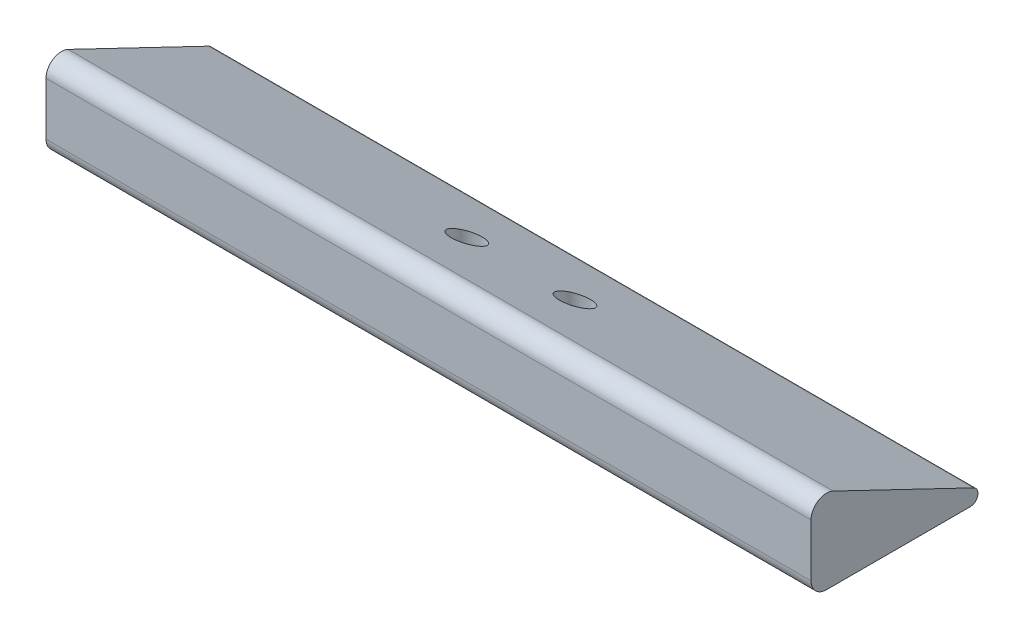
SolidWorks part; units mm, degrees
material "Rubber"
ref_plane "Front Plane" through (0, 0, 0) normal (0, 0, 1) x (1, 0, 0)
ref_plane "Top Plane" through (0, 0, 0) normal (0, 1, 0) x (1, 0, 0)
ref_plane "Right Plane" through (0, 0, 0) normal (1, 0, 0) x (0, 0, -1)
sketch "Sketch1" plane through (0, 0, 0) normal (1, 0, 0) x (0, 0, -1)
  line L0 (2, 0) -> (20.6058, 0)
  line L1 (21.0385, 1.9015) -> (2.8655, 10.6246)
  line L2 (0, 8.8215) -> (0, 2)
  arc A0 (0, 8.8215) -> (2.8655, 10.6246) centre (2, 8.8215) cw
  arc A1 (2, 0) -> (0, 2) centre (2, 2) cw
  arc A2 (21.0385, 1.9015) -> (20.6058, 0) centre (20.6058, 1) cw
  point P6 (0, 12)
  point P9 (0, 0)
  point P12 (25, 0)
  dimension "D1" = 12
  dimension "D3" = 2
  dimension "D4" = 1
  dimension "D2" = 25
extrude "Boss-Extrude1" add sketch "Sketch1" along normal blind 99
ref_plane "Plane1" through (0, 10, 0) normal (0, 1, 0) x (1, 0, 0)
sketch "Sketch2" plane through (0, 10, 0) normal (0, 1, 0) x (1, 0, 0)
  line L0 (99, 11.952) -> (0, 11.952) construction
  line L1 (99, 21.0385) -> (99, 2.8655) construction
  line L2 (0, 21.0385) -> (0, 2.8655) construction
  line L3 (49.5, 11.952) -> (49.5, 18.9766) construction
  circle A0 centre (42.5, 11.952) radius 2
  circle A1 centre (56.5, 11.952) radius 2
  dimension "D1" = 4
  dimension "D2" = 7
extrude "Cut-Extrude1" cut sketch "Sketch2" against normal blind 8
sketch "Sketch3" plane through (0, 2, 0) normal (0, 1, 0) x (1, 0, 0)
  circle A0 centre (42.5, 11.952) radius 1.5
  circle A1 centre (56.5, 11.952) radius 1.5
  dimension "D1" = 3
extrude "Cut-Extrude2" cut sketch "Sketch3" against normal through all
